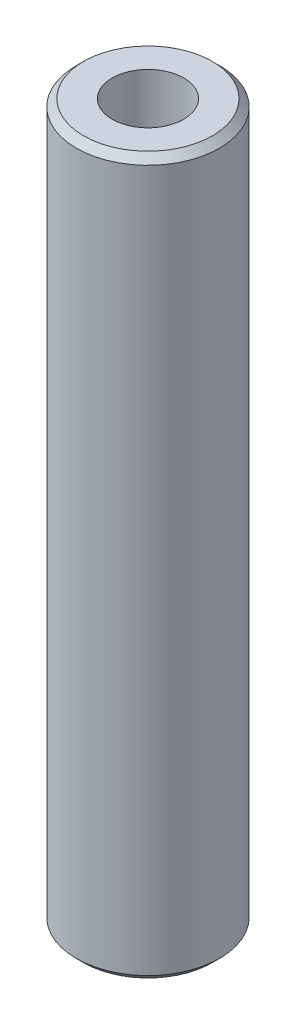
SolidWorks part; units mm, degrees
ref_plane "Front Plane" through (0, 0, 0) normal (0, 0, 1) x (1, 0, 0)
ref_plane "Top Plane" through (0, 0, 0) normal (0, 1, 0) x (1, 0, 0)
ref_plane "Right Plane" through (0, 0, 0) normal (1, 0, 0) x (0, 0, -1)
sketch "Sketch1" plane through (0, 0, 0) normal (0, 1, 0) x (1, 0, 0)
  circle A0 centre (0, 0) radius 10
  dimension "SHAFT_OD" = 20
extrude "Boss-Extrude1" add sketch "Sketch1" along normal blind 100
sketch "Sketch2" plane through (0, 0, 0) normal (0, 1, 0) x (1, 0, 0)
  circle A0 centre (0, 0) radius 5
  dimension "BORE_D" = 10
extrude "Cut-Extrude1" cut sketch "Sketch2" along normal through all
chamfer "Chamfer1" distance 1 angle 45 2 edges at (0, 100, 10) (0, 0, 10)
